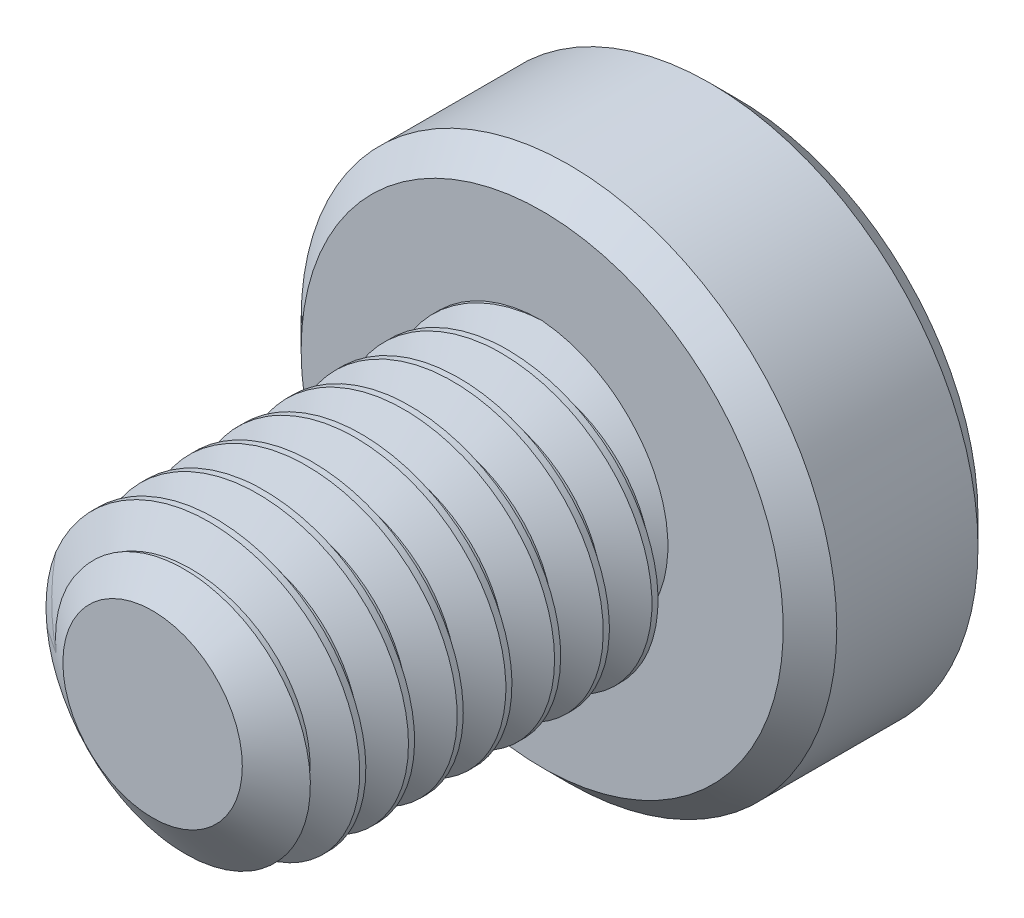
SolidWorks part; units mm, degrees
other "DetailItem1"
ref_plane "Front Plane" through (0, 0, 0) normal (0, 0, 1) x (1, 0, 0)
ref_plane "Top Plane" through (0, 0, 0) normal (0, 1, 0) x (1, 0, 0)
ref_plane "Right Plane" through (0, 0, 0) normal (1, 0, 0) x (0, 0, -1)
sketch "Sketch1" plane through (0, 0, 0) normal (0, 0, 1) x (1, 0, 0)
  circle A0 centre (0, 0) radius 1.5
  dimension "OD" = 3
extrude "Extrude1" add sketch "Sketch1" against normal blind 4
sketch "Sketch2" plane through (0, 0, 0) normal (0, 0, 1) x (1, 0, 0)
  circle A0 centre (0, 0) radius 1.5 construction
  circle A1 centre (0, 0) radius 1.5
curve "Helix/Spiral1" pitch 0.5 height 4.5 radius 1.5 centre (0, 0, 0) axis (0, 0, -1) start towards (0, 1, 0) parameters "pitch"=0.5
sketch "Sketch3" plane through (0, 0, 0) normal (1, 0, 0) x (0, 0, -1)
  line L0 (-0.4375, 1.5) -> (-0.25, 1.1752)
  line L1 (-0.25, 1.1752) -> (-0.1875, 1.1752)
  line L2 (-0.1875, 1.1752) -> (0, 1.5)
  line L3 (-0.4375, 1.5) -> (0, 1.5)
  line L4 (-0.2188, 1.5) -> (-0.2188, 1.1752) construction
  line L5 (-0.3438, 1.3376) -> (-0.0938, 1.3376) construction
  line L6 (0, 1.5) -> (0, -1.5) construction
  dimension "D1" = 0.0625
  dimension "D2" = 0.25
  dimension "D3" = 60
sweep "Cut-Sweep1" cut profiles "Sketch3" path "Helix/Spiral1"
sketch "Sketch4" plane through (0, 0, 0) normal (1, 0, 0) x (0, 0, -1)
  line L0 (0.4053, 1.5) -> (0, 0.9212)
  line L1 (0, 0.9212) -> (0, 1.5)
  line L2 (0.4053, 1.5) -> (0, 1.5)
  line L3 (-0.4375, 1.5) -> (0, 1.5) construction
  line L4 (0, 0) -> (7.0209, 0) construction
  dimension "D1" = 55
  dimension "D2" = 0.254
revolve "Cut-Revolve1" cut sketch "Sketch4" angle 360 about L4
sketch "Sketch6" plane through (0, 0, -4) normal (0, 0, -1) x (-1, 0, 0)
  circle A0 centre (0, 0) radius 2.75
  dimension "head dia" = 5.5
extrude "Extrude2" add sketch "Sketch6" along normal blind 2
sketch "Sketch7" plane through (0, 0, -6) normal (0, 0, -1) x (-1, 0, 0)
  line L1 (0, 1.1547) -> (-1, 0.5774)
  line L2 (-1, 0.5774) -> (-1, -0.5774)
  line L3 (-1, -0.5774) -> (0, -1.1547)
  line L4 (0, -1.1547) -> (1, -0.5774)
  line L5 (1, -0.5774) -> (1, 0.5774)
  line L6 (1, 0.5774) -> (0, 1.1547)
  circle A0 centre (0, 0) radius 1 construction
  dimension "hex dia" = 2
extrude "Cut-Extrude1" cut sketch "Sketch7" against normal blind 1.5
sketch "Sketch8" plane through (0, 0, -6) normal (0, 0, -1) x (-1, 0, 0)
  circle A0 centre (0, 0) radius 1.1547
extrude "Cut-Extrude2" cut sketch "Sketch8" against normal through all draft 45
chamfer "Chamfer1" distance 0.275 angle 45 2 edges at (-2.75, 0, -6) (-2.75, 0, -4)
sketch "Sketch10" plane through (0, 0, -4) normal (0, 0, 1) x (1, 0, 0)
  circle A1 centre (0, 0) radius 1.5
  circle A2 centre (0, 0) radius 1.5
  dimension "D1" = 0
ref_plane "Plane1" through (0, 0, -30) normal (0, 0, 1) x (1, 0, 0)
extrude "partial thread" [suppressed] add sketch "Sketch10" along normal up to surface (20 mm away) separate body up to plane "Plane1"
chamfer "Chamfer2" [suppressed] distance 0.06 angle 45
combine bodies "Combine1" [suppressed] operation type add bodies to combine 107 108
sketch "Sketch9" plane through (0, 0, 0) normal (1, 0, 0) x (0, 0, -1)
  line L0 (0, 1.5) -> (0, -1.5) construction
  line L1 (1.25, 1.5) -> (1.25, -1.5) construction
  dimension "D1" = 1.25
  dimension "D4" = 0.635
  dimension "D5" = 0.3302
equation "\"D3@Helix/Spiral1\" = \"screw length@Extrude1\"+\"pitch@Helix/Spiral1\""
equation "\"D1@Sketch3\" = \"pitch@Helix/Spiral1\"*.125"
equation "\"D2@Sketch3\" = \"pitch@Helix/Spiral1\"*.5"
equation "\"D1@Cut-Extrude1\" = \"hex dia@Sketch7\"*.75"
equation "\"D1@Chamfer1\" = \"head dia@Sketch6\"*.05"
equation "\"D1@Sketch9\" = \"pitch@Helix/Spiral1\"*2.5"
equation "\"D1@Chamfer2\"=\"OD@Sketch1\"*.02"
